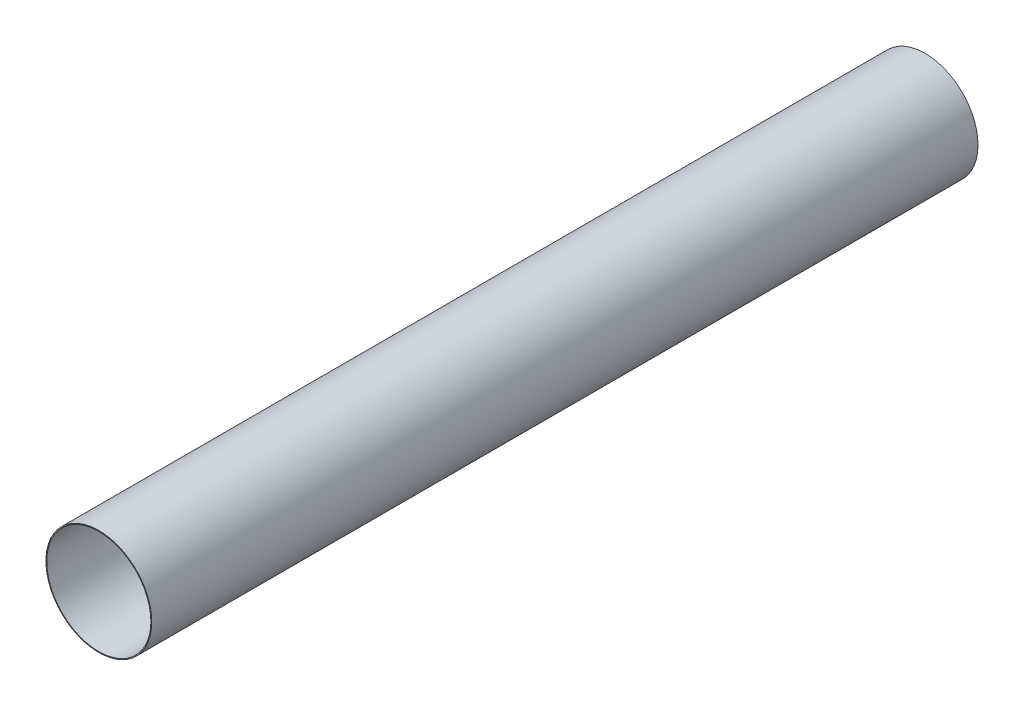
SolidWorks part; units mm, degrees
ref_plane "Plan de face" through (0, 0, 0) normal (0, 0, 1) x (1, 0, 0)
ref_plane "Plan de dessus" through (0, 0, 0) normal (0, 1, 0) x (1, 0, 0)
ref_plane "Plan de droite" through (0, 0, 0) normal (1, 0, 0) x (0, 0, -1)
sketch "Esquisse1" plane through (0, 0, 0) normal (0, 0, 1) x (1, 0, 0)
  circle A2 centre (0, 0) radius 76.182
  circle A3 centre (0, 0) radius 75
  dimension "D1" = 150
  dimension "D2" = 152.364
extrude "Boss.-Extru.1" add sketch "Esquisse1" along normal blind 1190 contours A2 | A3
equation "\"D1@Boss.-Extru.1\"=1190"
equation "\"d_body\"= 150mm'rocket composite body diameter (RORO II)"
equation "\"t_body\"= 1.182mm'rocket composite body thickness (RORO II)"
equation "\"l_upper_body\"= 1150mm'upper body length (as of RORO I)"
equation "\"D1@Esquisse1\"=\"d_body\""
equation "\"D2@Esquisse1\"=\"d_body\"+2*\"t_body\""
